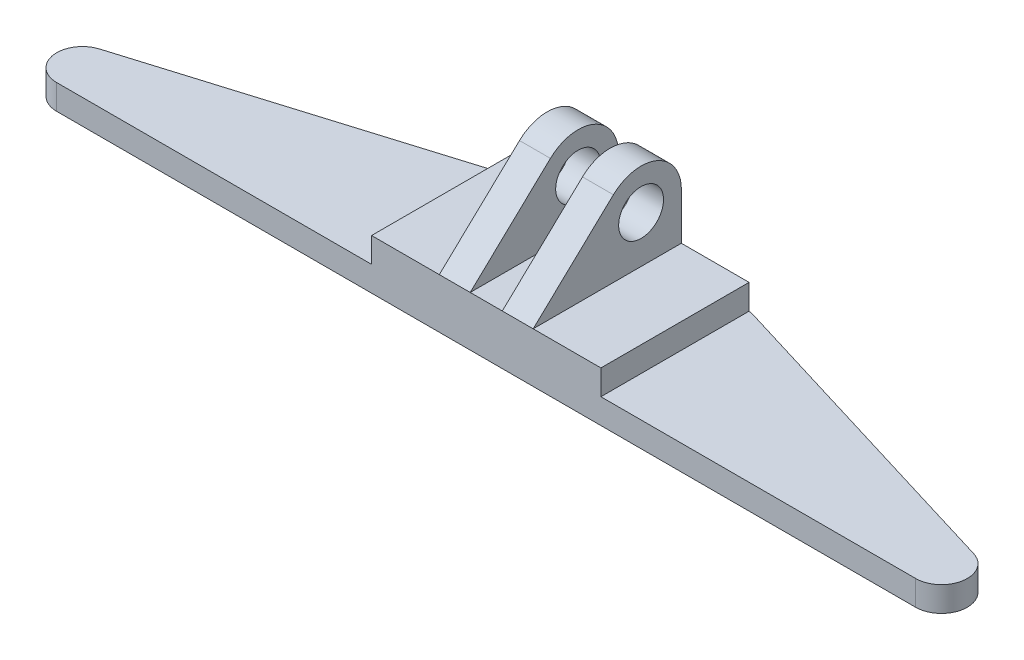
SolidWorks part; units mm, degrees
material "6061-T6 (SS)"
ref_plane "Front Plane" through (0, 0, 0) normal (0, 0, 1) x (1, 0, 0)
ref_plane "Top Plane" through (0, 0, 0) normal (0, 1, 0) x (1, 0, 0)
ref_plane "Right Plane" through (0, 0, 0) normal (1, 0, 0) x (0, 0, -1)
sketch "Sketch1" plane through (0, 0, 0) normal (0, 1, 0) x (1, 0, 0)
  line L0 (5.0717, 14.0025) -> (94.4245, 41.2115)
  line L1 (7.1564, 0) -> (245.256, 0)
  line L3 (94.4245, 41.2115) -> (157.988, 41.2115)
  line L5 (247.3408, 14.0025) -> (157.988, 41.2115)
  line L6 (94.4245, 41.2115) -> (94.4245, 60.7078) construction
  line L7 (94.4245, 60.7078) -> (157.988, 60.7078) construction
  line L8 (157.988, 60.7078) -> (157.988, 41.2115) construction
  arc A0 (5.0717, 14.0025) -> (7.1564, 0) centre (7.1564, 7.1564) ccw
  arc A1 (245.256, 0) -> (247.3408, 14.0025) centre (245.256, 7.1564) ccw
  dimension "D3" = 14.3129
  dimension "D4" = 14.3129
  dimension "D5" = 63.5635
extrude "Boss-Extrude1" add sketch "Sketch1" along normal blind 6.9215
fillet "Fillet1" radius 12.7 2 edges at (94.4245, 3.4608, -41.2115) (157.988, 3.4608, -41.2115)
sketch "Sketch2" plane through (0, 6.9215, 0) normal (0, 1, 0) x (1, 0, 0)
  line L0 (7.1564, 0) -> (245.256, 0) construction
  line L1 (94.4451, 41.073) -> (158.0086, 41.073)
  line L2 (94.4451, 41.073) -> (94.4451, 0)
  line L3 (94.4451, 0) -> (158.0086, 0)
  line L4 (158.0086, 41.073) -> (158.0086, 0)
  arc A0 (96.3153, 41.2115) -> (92.6157, 40.6607) centre (96.3153, 28.5115) ccw construction
  dimension "D1" = 63.5635
extrude "Boss-Extrude2" add sketch "Sketch2" along normal blind 6.9215
sketch "Sketch3" plane through (94.4451, 0, 0) normal (-1, 0, 0) x (0, 0, 1)
  line L0 (-51.1842, 37.973) -> (7.3835, 37.973) construction
  line L1 (-41.073, 13.843) -> (0, 13.843) construction
  line L2 (-41.073, 7.7795) -> (-41.073, 52.3209) construction
  line L3 (-41.073, 13.843) -> (-41.073, 6.9215) construction
  line L4 (-41.073, 26.8097) -> (-41.073, 13.843)
  line L5 (-41.073, 13.843) -> (0, 13.843)
  line L6 (0, 13.843) -> (-22.2306, 34.9122)
  arc A0 (-22.2306, 34.9122) -> (-41.073, 26.8097) centre (-29.9097, 26.8097) ccw
  circle A1 centre (-29.9097, 26.8097) radius 6.223
  dimension "D1" = 22.3266
  dimension "D2" = 24.13
  dimension "D3" = 12.446
extrude "Boss-Extrude4" add sketch "Sketch3" against normal offset from surface (44.7929 mm away) 18.7706 up to face at (158.0086, 9.6901, -24.6426)
extrude "Cut-Extrude1" cut sketch "Sketch3<2>" against normal blind 18.7706
sketch "Sketch3<2>" plane through (94.4451, 0, 0) normal (-1, 0, 0) x (0, 0, 1) same geometry as "Sketch3"
sketch "Sketch4" plane through (0, 0, 0) normal (0, 0, 1) x (1, 0, 0)
  line L0 (113.2157, 13.843) -> (139.238, 13.843) construction
  line L1 (121.7819, 13.843) -> (130.6719, 13.843)
  line L2 (121.7819, 13.843) -> (121.7819, 37.973)
  line L3 (121.7819, 37.973) -> (130.6719, 37.973)
  line L4 (130.6719, 13.843) -> (130.6719, 37.973)
  line L5 (139.238, 37.973) -> (113.2157, 37.973) construction
  point P8 (126.2269, 37.973)
  point P9 (126.2269, 13.843)
  dimension "D1" = 8.89
extrude "Cut-Extrude2" cut sketch "Sketch4" against normal through all
